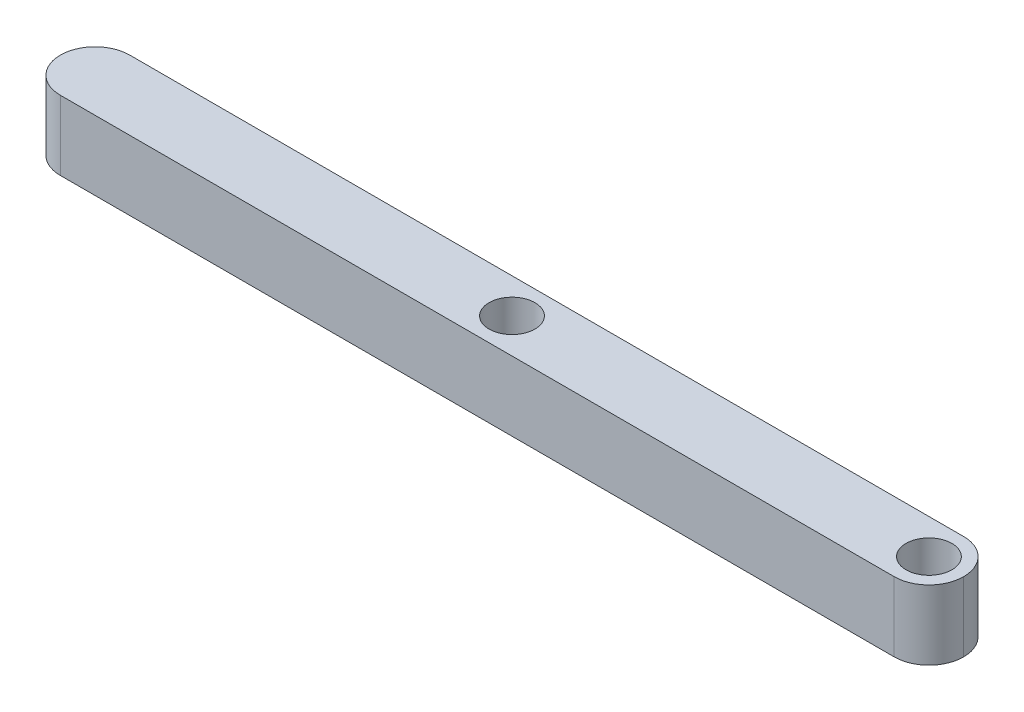
SolidWorks part; units mm, degrees
ref_plane "前视基准面" through (0, 0, 0) normal (0, 0, 1) x (1, 0, 0)
ref_plane "上视基准面" through (0, 0, 0) normal (0, 1, 0) x (1, 0, 0)
ref_plane "右视基准面" through (0, 0, 0) normal (1, 0, 0) x (0, 0, -1)
sketch "草图1" plane through (0, 0, 0) normal (0, 1, 0) x (1, 0, 0)
  line L1 (0, 0) -> (650, 0)
  line L2 (0, 0) -> (0, 50)
  line L3 (0, 50) -> (650, 50)
  line L4 (650, 0) -> (650, 50)
  circle A1 centre (625, 25) radius 16.5
  circle A3 centre (325, 25) radius 16.5
  dimension "D4" = 33
  dimension "D5" = 33
  dimension "D1" = 25
  dimension "D2" = 50
  dimension "D6" = 650
  dimension "D8" = 25
  dimension "D10" = 300
extrude "凸台-拉伸1" add sketch "草图1" along normal blind 50
fillet "圆角1" radius 25 4 edges at (0, 25, -50) (0, 25, 0) (650, 25, -50) (650, 25, 0)
